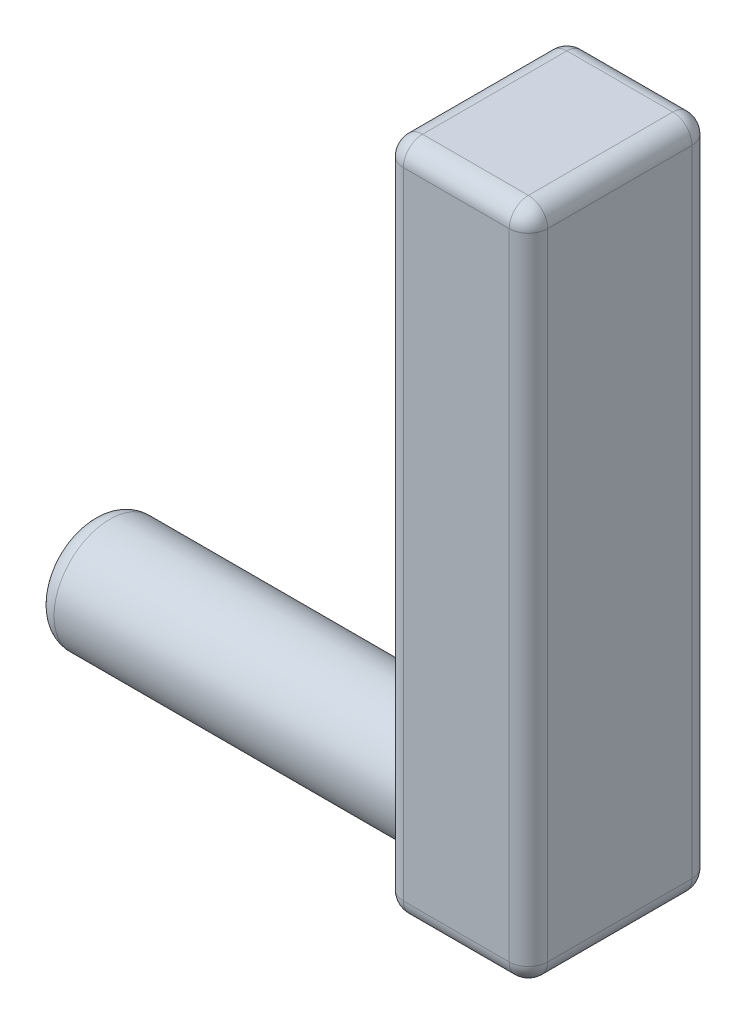
SolidWorks part; units mm, degrees
ref_plane "Front Plane" through (0, 0, 0) normal (0, 0, 1) x (1, 0, 0)
ref_plane "Top Plane" through (0, 0, 0) normal (0, 1, 0) x (1, 0, 0)
ref_plane "Right Plane" through (0, 0, 0) normal (1, 0, 0) x (0, 0, -1)
sketch "Sketch1" plane through (0, 0, 0) normal (1, 0, 0) x (0, 0, -1)
  line L1 (0, 0) -> (12.065, 0)
  line L2 (0, 0) -> (0, 44.45)
  line L3 (0, 44.45) -> (12.065, 44.45)
  line L4 (12.065, 0) -> (12.065, 44.45)
  dimension "D1" = 12.065
  dimension "D2" = 44.45
extrude "Boss-Extrude1" add sketch "Sketch1" along normal blind 9.525
sketch "Sketch2" plane through (0, 0, 0) normal (-1, 0, 0) x (0, 0, 1)
  line L0 (0, 0) -> (-12.065, 0) construction
  line L1 (-12.065, 0) -> (0, 0) construction
  circle A0 centre (-6.0325, 3.683) radius 3.683
  point P5 (-6.0325, 0)
  dimension "D1" = 7.366
extrude "Boss-Extrude2" add sketch "Sketch2" along normal blind 25.4
fillet "Fillet1" radius 1.27 14 edges at (9.525, 0, -6.0325) (0, 0, -9.0488) (0, 0, -3.0162) (4.7625, 0, -12.065) (9.525, 22.225, -12.065) (4.7625, 44.45, -12.065) (0, 22.225, -12.065) (4.7625, 44.45, 0) (9.525, 22.225, 0) (4.7625, 0, 0) (0, 22.225, 0) (9.525, 44.45, -6.0325) (0, 44.45, -6.0325) (-25.4, 3.683, -2.3495)
